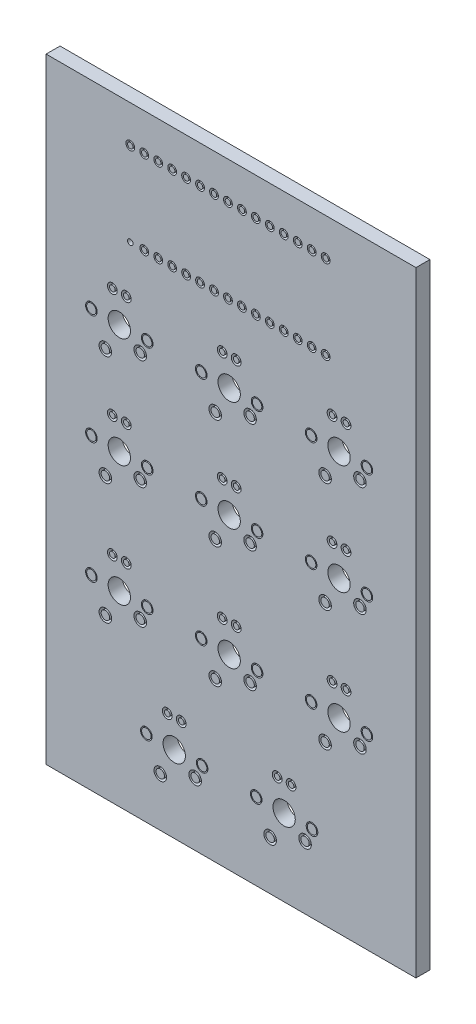
SolidWorks part; units mm, degrees
ref_plane "Front Plane" through (0, 0, 0) normal (0, 0, 1) x (1, 0, 0)
ref_plane "Top Plane" through (0, 0, 0) normal (0, 1, 0) x (1, 0, 0)
ref_plane "Right Plane" through (0, 0, 0) normal (1, 0, 0) x (0, 0, -1)
sketch "Sketch2" plane through (0, 0, 0) normal (0, 0, 1) x (1, 0, 0)
  line L1 (0.6731, 111.9988) -> (68.0009, 111.9988)
  line L2 (68.0009, 111.9988) -> (68.0009, 0)
  line L3 (68.0009, 0) -> (0.6731, 0)
  line L4 (0.6731, 0) -> (0.6731, 40.5511)
  line L5 (0.6731, 40.5511) -> (0.6731, 111.9988)
  line L6 (17.8075, 52.698) -> (17.8125, 52.698)
  line L8 (17.8075, 54.222) -> (17.8125, 54.222)
  line L10 (11.4575, 50.158) -> (11.4625, 50.158)
  line L12 (11.4575, 51.682) -> (11.4625, 51.682)
  line L14 (19.0775, 55.1427) -> (19.0825, 55.1427)
  line L16 (19.0775, 56.8572) -> (19.0825, 56.8572)
  line L18 (8.9175, 55.1427) -> (8.9225, 55.1427)
  line L20 (8.9175, 56.8572) -> (8.9225, 56.8572)
  line L22 (15.2675, 60.572) -> (15.2725, 60.572)
  line L24 (15.2675, 61.588) -> (15.2725, 61.588)
  line L26 (12.7275, 60.572) -> (12.7325, 60.572)
  line L28 (12.7275, 61.588) -> (12.7325, 61.588)
  line L30 (37.8074, 52.698) -> (37.8125, 52.698)
  line L32 (37.8074, 54.222) -> (37.8125, 54.222)
  line L34 (31.4574, 50.158) -> (31.4625, 50.158)
  line L36 (31.4574, 51.682) -> (31.4625, 51.682)
  line L38 (39.0774, 55.1427) -> (39.0825, 55.1427)
  line L40 (39.0774, 56.8572) -> (39.0825, 56.8572)
  line L42 (28.9174, 55.1427) -> (28.9225, 55.1427)
  line L44 (28.9174, 56.8572) -> (28.9225, 56.8572)
  line L46 (35.2674, 60.572) -> (35.2725, 60.572)
  line L48 (35.2674, 61.588) -> (35.2725, 61.588)
  line L50 (32.7274, 60.572) -> (32.7325, 60.572)
  line L52 (32.7274, 61.588) -> (32.7325, 61.588)
  line L54 (17.8075, 30.698) -> (17.8125, 30.698)
  line L56 (17.8075, 32.222) -> (17.8125, 32.222)
  line L58 (11.4575, 28.158) -> (11.4625, 28.158)
  line L60 (11.4575, 29.682) -> (11.4625, 29.682)
  line L62 (19.0775, 33.1427) -> (19.0825, 33.1427)
  line L64 (19.0775, 34.8572) -> (19.0825, 34.8572)
  line L66 (8.9175, 33.1427) -> (8.9225, 33.1427)
  line L68 (8.9175, 34.8572) -> (8.9225, 34.8572)
  line L70 (15.2675, 38.572) -> (15.2725, 38.572)
  line L72 (15.2675, 39.588) -> (15.2725, 39.588)
  line L74 (12.7275, 38.572) -> (12.7325, 38.572)
  line L76 (12.7275, 39.588) -> (12.7325, 39.588)
  line L78 (37.8074, 30.698) -> (37.8125, 30.698)
  line L80 (37.8074, 32.222) -> (37.8125, 32.222)
  line L82 (31.4574, 28.158) -> (31.4625, 28.158)
  line L84 (31.4574, 29.682) -> (31.4625, 29.682)
  line L86 (39.0774, 33.1427) -> (39.0825, 33.1427)
  line L88 (39.0774, 34.8572) -> (39.0825, 34.8572)
  line L90 (28.9174, 33.1427) -> (28.9225, 33.1427)
  line L92 (28.9174, 34.8572) -> (28.9225, 34.8572)
  line L94 (35.2674, 38.572) -> (35.2725, 38.572)
  line L96 (35.2674, 39.588) -> (35.2725, 39.588)
  line L98 (32.7274, 38.572) -> (32.7325, 38.572)
  line L100 (32.7274, 39.588) -> (32.7325, 39.588)
  line L102 (57.8075, 52.698) -> (57.8125, 52.698)
  line L104 (57.8075, 54.222) -> (57.8125, 54.222)
  line L106 (51.4575, 50.158) -> (51.4625, 50.158)
  line L108 (51.4575, 51.682) -> (51.4625, 51.682)
  line L110 (59.0775, 55.1427) -> (59.0825, 55.1427)
  line L112 (59.0775, 56.8572) -> (59.0825, 56.8572)
  line L114 (48.9175, 55.1427) -> (48.9225, 55.1427)
  line L116 (48.9175, 56.8572) -> (48.9225, 56.8572)
  line L118 (55.2675, 60.572) -> (55.2725, 60.572)
  line L120 (55.2675, 61.588) -> (55.2725, 61.588)
  line L122 (52.7275, 60.572) -> (52.7325, 60.572)
  line L124 (52.7275, 61.588) -> (52.7325, 61.588)
  line L126 (57.8075, 30.698) -> (57.8125, 30.698)
  line L128 (57.8075, 32.222) -> (57.8125, 32.222)
  line L130 (51.4575, 28.158) -> (51.4625, 28.158)
  line L132 (51.4575, 29.682) -> (51.4625, 29.682)
  line L134 (59.0775, 33.1427) -> (59.0825, 33.1427)
  line L136 (59.0775, 34.8572) -> (59.0825, 34.8572)
  line L138 (48.9175, 33.1427) -> (48.9225, 33.1427)
  line L140 (48.9175, 34.8572) -> (48.9225, 34.8572)
  line L142 (55.2675, 38.572) -> (55.2725, 38.572)
  line L144 (55.2675, 39.588) -> (55.2725, 39.588)
  line L146 (52.7275, 38.572) -> (52.7325, 38.572)
  line L148 (52.7275, 39.588) -> (52.7325, 39.588)
  line L150 (27.8074, 10.698) -> (27.8125, 10.698)
  line L152 (27.8074, 12.222) -> (27.8125, 12.222)
  line L154 (21.4574, 8.158) -> (21.4625, 8.158)
  line L156 (21.4574, 9.682) -> (21.4625, 9.682)
  line L158 (29.0774, 13.1427) -> (29.0825, 13.1427)
  line L160 (29.0774, 14.8572) -> (29.0825, 14.8572)
  line L162 (18.9174, 13.1427) -> (18.9225, 13.1427)
  line L164 (18.9174, 14.8572) -> (18.9225, 14.8572)
  line L166 (25.2674, 18.572) -> (25.2725, 18.572)
  line L168 (25.2674, 19.588) -> (25.2725, 19.588)
  line L170 (22.7274, 18.572) -> (22.7325, 18.572)
  line L172 (22.7274, 19.588) -> (22.7325, 19.588)
  line L174 (47.8074, 10.698) -> (47.8125, 10.698)
  line L176 (47.8074, 12.222) -> (47.8125, 12.222)
  line L178 (41.4574, 8.158) -> (41.4625, 8.158)
  line L180 (41.4574, 9.682) -> (41.4625, 9.682)
  line L182 (49.0774, 13.1427) -> (49.0825, 13.1427)
  line L184 (49.0774, 14.8572) -> (49.0825, 14.8572)
  line L186 (38.9174, 13.1427) -> (38.9225, 13.1427)
  line L188 (38.9174, 14.8572) -> (38.9225, 14.8572)
  line L190 (45.2674, 18.572) -> (45.2725, 18.572)
  line L192 (45.2674, 19.588) -> (45.2725, 19.588)
  line L194 (42.7274, 18.572) -> (42.7325, 18.572)
  line L196 (42.7274, 19.588) -> (42.7325, 19.588)
  line L198 (17.8075, 72.698) -> (17.8125, 72.698)
  line L200 (17.8075, 74.222) -> (17.8125, 74.222)
  line L202 (11.4575, 70.158) -> (11.4625, 70.158)
  line L204 (11.4575, 71.682) -> (11.4625, 71.682)
  line L206 (19.0775, 75.1428) -> (19.0825, 75.1428)
  line L208 (19.0775, 76.8573) -> (19.0825, 76.8573)
  line L210 (8.9175, 75.1428) -> (8.9225, 75.1428)
  line L212 (8.9175, 76.8573) -> (8.9225, 76.8573)
  line L214 (15.2675, 80.572) -> (15.2725, 80.572)
  line L216 (15.2675, 81.588) -> (15.2725, 81.588)
  line L218 (12.7275, 80.572) -> (12.7325, 80.572)
  line L220 (12.7275, 81.588) -> (12.7325, 81.588)
  line L222 (37.8074, 72.698) -> (37.8125, 72.698)
  line L224 (37.8074, 74.222) -> (37.8125, 74.222)
  line L226 (31.4574, 70.158) -> (31.4625, 70.158)
  line L228 (31.4574, 71.682) -> (31.4625, 71.682)
  line L230 (39.0774, 75.1428) -> (39.0825, 75.1428)
  line L232 (39.0774, 76.8573) -> (39.0825, 76.8573)
  line L234 (28.9174, 75.1428) -> (28.9225, 75.1428)
  line L236 (28.9174, 76.8573) -> (28.9225, 76.8573)
  line L238 (35.2674, 80.572) -> (35.2725, 80.572)
  line L240 (35.2674, 81.588) -> (35.2725, 81.588)
  line L242 (32.7274, 80.572) -> (32.7325, 80.572)
  line L244 (32.7274, 81.588) -> (32.7325, 81.588)
  line L246 (57.8075, 72.698) -> (57.8125, 72.698)
  line L248 (57.8075, 74.222) -> (57.8125, 74.222)
  line L250 (51.4575, 70.158) -> (51.4625, 70.158)
  line L252 (51.4575, 71.682) -> (51.4625, 71.682)
  line L254 (59.0775, 75.1428) -> (59.0825, 75.1428)
  line L256 (59.0775, 76.8573) -> (59.0825, 76.8573)
  line L258 (48.9175, 75.1428) -> (48.9225, 75.1428)
  line L260 (48.9175, 76.8573) -> (48.9225, 76.8573)
  line L262 (55.2675, 80.572) -> (55.2725, 80.572)
  line L264 (55.2675, 81.588) -> (55.2725, 81.588)
  line L266 (52.7275, 80.572) -> (52.7325, 80.572)
  line L268 (52.7275, 81.588) -> (52.7325, 81.588)
  circle A0 centre (18.54, 90) radius 0.5
  circle A1 centre (18.54, 90) radius 0.8
  circle A2 centre (21.08, 90) radius 0.5
  circle A3 centre (21.08, 90) radius 0.8
  circle A4 centre (23.62, 90) radius 0.5
  circle A5 centre (23.62, 90) radius 0.8
  circle A6 centre (26.16, 90) radius 0.5
  circle A7 centre (26.16, 90) radius 0.8
  circle A8 centre (28.7, 90) radius 0.5
  circle A9 centre (28.7, 90) radius 0.8
  circle A10 centre (31.24, 90) radius 0.5
  circle A11 centre (31.24, 90) radius 0.8
  circle A12 centre (33.78, 90) radius 0.5
  circle A13 centre (33.78, 90) radius 0.8
  circle A14 centre (36.32, 90) radius 0.5
  circle A15 centre (36.32, 90) radius 0.8
  circle A16 centre (38.86, 90) radius 0.5
  circle A17 centre (38.86, 90) radius 0.8
  circle A18 centre (41.4, 90) radius 0.5
  circle A19 centre (41.4, 90) radius 0.8
  circle A20 centre (43.94, 90) radius 0.5
  circle A21 centre (43.94, 90) radius 0.8
  circle A22 centre (46.48, 90) radius 0.5
  circle A23 centre (46.48, 90) radius 0.8
  circle A24 centre (49.02, 90) radius 0.5
  circle A25 centre (49.02, 90) radius 0.8
  circle A26 centre (51.56, 90) radius 0.5
  circle A27 centre (51.56, 90) radius 0.8
  circle A28 centre (51.56, 105.24) radius 0.5
  circle A29 centre (51.56, 105.24) radius 0.8
  circle A30 centre (49.02, 105.24) radius 0.5
  circle A31 centre (49.02, 105.24) radius 0.8
  circle A32 centre (46.48, 105.24) radius 0.5
  circle A33 centre (46.48, 105.24) radius 0.8
  circle A34 centre (43.94, 105.24) radius 0.5
  circle A35 centre (43.94, 105.24) radius 0.8
  circle A36 centre (41.4, 105.24) radius 0.5
  circle A37 centre (41.4, 105.24) radius 0.8
  circle A38 centre (38.86, 105.24) radius 0.5
  circle A39 centre (38.86, 105.24) radius 0.8
  circle A40 centre (36.32, 105.24) radius 0.5
  circle A41 centre (36.32, 105.24) radius 0.8
  circle A42 centre (33.78, 105.24) radius 0.5
  circle A43 centre (33.78, 105.24) radius 0.8
  circle A44 centre (31.24, 105.24) radius 0.5
  circle A45 centre (31.24, 105.24) radius 0.8
  circle A46 centre (28.7, 105.24) radius 0.5
  circle A47 centre (28.7, 105.24) radius 0.8
  circle A48 centre (26.16, 105.24) radius 0.5
  circle A49 centre (26.16, 105.24) radius 0.8
  circle A50 centre (23.62, 105.24) radius 0.5
  circle A51 centre (23.62, 105.24) radius 0.8
  circle A52 centre (21.08, 105.24) radius 0.5
  circle A53 centre (21.08, 105.24) radius 0.8
  circle A54 centre (18.54, 105.24) radius 0.5
  circle A55 centre (18.54, 105.24) radius 0.8
  circle A56 centre (16, 105.24) radius 0.5
  circle A57 centre (16, 105.24) radius 0.8
  arc A58 (17.8125, 52.698) -> (17.8125, 54.222) centre (17.8125, 53.46) ccw
  arc A59 (17.8075, 54.222) -> (17.8075, 52.698) centre (17.8075, 53.46) ccw
  circle A60 centre (17.81, 53.46) radius 1.143
  arc A61 (11.4625, 50.158) -> (11.4625, 51.682) centre (11.4625, 50.92) ccw
  arc A62 (11.4575, 51.682) -> (11.4575, 50.158) centre (11.4575, 50.92) ccw
  circle A63 centre (11.46, 50.92) radius 1.143
  arc A64 (19.0825, 55.1427) -> (19.0825, 56.8572) centre (19.0825, 56) ccw
  arc A65 (19.0775, 56.8572) -> (19.0775, 55.1427) centre (19.0775, 56) ccw
  circle A66 centre (19.08, 56) radius 1.0571
  arc A67 (8.9225, 55.1427) -> (8.9225, 56.8572) centre (8.9225, 56) ccw
  arc A68 (8.9175, 56.8572) -> (8.9175, 55.1427) centre (8.9175, 56) ccw
  circle A69 centre (8.92, 56) radius 1.0571
  arc A70 (15.2725, 60.572) -> (15.2725, 61.588) centre (15.2725, 61.08) ccw
  arc A71 (15.2675, 61.588) -> (15.2675, 60.572) centre (15.2675, 61.08) ccw
  circle A72 centre (15.27, 61.08) radius 0.889
  arc A73 (12.7325, 60.572) -> (12.7325, 61.588) centre (12.7325, 61.08) ccw
  arc A74 (12.7275, 61.588) -> (12.7275, 60.572) centre (12.7275, 61.08) ccw
  circle A75 centre (12.73, 61.08) radius 0.889
  arc A76 (37.8125, 52.698) -> (37.8125, 54.222) centre (37.8125, 53.46) ccw
  arc A77 (37.8074, 54.222) -> (37.8074, 52.698) centre (37.8074, 53.46) ccw
  circle A78 centre (37.81, 53.46) radius 1.143
  arc A79 (31.4625, 50.158) -> (31.4625, 51.682) centre (31.4625, 50.92) ccw
  arc A80 (31.4574, 51.682) -> (31.4574, 50.158) centre (31.4574, 50.92) ccw
  circle A81 centre (31.46, 50.92) radius 1.143
  arc A82 (39.0825, 55.1427) -> (39.0825, 56.8572) centre (39.0825, 56) ccw
  arc A83 (39.0774, 56.8572) -> (39.0774, 55.1427) centre (39.0774, 56) ccw
  circle A84 centre (39.08, 56) radius 1.0571
  arc A85 (28.9225, 55.1427) -> (28.9225, 56.8572) centre (28.9225, 56) ccw
  arc A86 (28.9174, 56.8572) -> (28.9174, 55.1427) centre (28.9174, 56) ccw
  circle A87 centre (28.92, 56) radius 1.0571
  arc A88 (35.2725, 60.572) -> (35.2725, 61.588) centre (35.2725, 61.08) ccw
  arc A89 (35.2674, 61.588) -> (35.2674, 60.572) centre (35.2674, 61.08) ccw
  circle A90 centre (35.27, 61.08) radius 0.889
  arc A91 (32.7325, 60.572) -> (32.7325, 61.588) centre (32.7325, 61.08) ccw
  arc A92 (32.7274, 61.588) -> (32.7274, 60.572) centre (32.7274, 61.08) ccw
  circle A93 centre (32.73, 61.08) radius 0.889
  arc A94 (17.8125, 30.698) -> (17.8125, 32.222) centre (17.8125, 31.46) ccw
  arc A95 (17.8075, 32.222) -> (17.8075, 30.698) centre (17.8075, 31.46) ccw
  circle A96 centre (17.81, 31.46) radius 1.143
  arc A97 (11.4625, 28.158) -> (11.4625, 29.682) centre (11.4625, 28.92) ccw
  arc A98 (11.4575, 29.682) -> (11.4575, 28.158) centre (11.4575, 28.92) ccw
  circle A99 centre (11.46, 28.92) radius 1.143
  arc A100 (19.0825, 33.1427) -> (19.0825, 34.8572) centre (19.0825, 34) ccw
  arc A101 (19.0775, 34.8572) -> (19.0775, 33.1427) centre (19.0775, 34) ccw
  circle A102 centre (19.08, 34) radius 1.0571
  arc A103 (8.9225, 33.1427) -> (8.9225, 34.8572) centre (8.9225, 34) ccw
  arc A104 (8.9175, 34.8572) -> (8.9175, 33.1427) centre (8.9175, 34) ccw
  circle A105 centre (8.92, 34) radius 1.0571
  arc A106 (15.2725, 38.572) -> (15.2725, 39.588) centre (15.2725, 39.08) ccw
  arc A107 (15.2675, 39.588) -> (15.2675, 38.572) centre (15.2675, 39.08) ccw
  circle A108 centre (15.27, 39.08) radius 0.889
  arc A109 (12.7325, 38.572) -> (12.7325, 39.588) centre (12.7325, 39.08) ccw
  arc A110 (12.7275, 39.588) -> (12.7275, 38.572) centre (12.7275, 39.08) ccw
  circle A111 centre (12.73, 39.08) radius 0.889
  arc A112 (37.8125, 30.698) -> (37.8125, 32.222) centre (37.8125, 31.46) ccw
  arc A113 (37.8074, 32.222) -> (37.8074, 30.698) centre (37.8074, 31.46) ccw
  circle A114 centre (37.81, 31.46) radius 1.143
  arc A115 (31.4625, 28.158) -> (31.4625, 29.682) centre (31.4625, 28.92) ccw
  arc A116 (31.4574, 29.682) -> (31.4574, 28.158) centre (31.4574, 28.92) ccw
  circle A117 centre (31.46, 28.92) radius 1.143
  arc A118 (39.0825, 33.1427) -> (39.0825, 34.8572) centre (39.0825, 34) ccw
  arc A119 (39.0774, 34.8572) -> (39.0774, 33.1427) centre (39.0774, 34) ccw
  circle A120 centre (39.08, 34) radius 1.0571
  arc A121 (28.9225, 33.1427) -> (28.9225, 34.8572) centre (28.9225, 34) ccw
  arc A122 (28.9174, 34.8572) -> (28.9174, 33.1427) centre (28.9174, 34) ccw
  circle A123 centre (28.92, 34) radius 1.0571
  arc A124 (35.2725, 38.572) -> (35.2725, 39.588) centre (35.2725, 39.08) ccw
  arc A125 (35.2674, 39.588) -> (35.2674, 38.572) centre (35.2674, 39.08) ccw
  circle A126 centre (35.27, 39.08) radius 0.889
  arc A127 (32.7325, 38.572) -> (32.7325, 39.588) centre (32.7325, 39.08) ccw
  arc A128 (32.7274, 39.588) -> (32.7274, 38.572) centre (32.7274, 39.08) ccw
  circle A129 centre (32.73, 39.08) radius 0.889
  arc A130 (57.8125, 52.698) -> (57.8125, 54.222) centre (57.8125, 53.46) ccw
  arc A131 (57.8075, 54.222) -> (57.8075, 52.698) centre (57.8075, 53.46) ccw
  circle A132 centre (57.81, 53.46) radius 1.143
  arc A133 (51.4625, 50.158) -> (51.4625, 51.682) centre (51.4625, 50.92) ccw
  arc A134 (51.4575, 51.682) -> (51.4575, 50.158) centre (51.4575, 50.92) ccw
  circle A135 centre (51.46, 50.92) radius 1.143
  arc A136 (59.0825, 55.1427) -> (59.0825, 56.8572) centre (59.0825, 56) ccw
  arc A137 (59.0775, 56.8572) -> (59.0775, 55.1427) centre (59.0775, 56) ccw
  circle A138 centre (59.08, 56) radius 1.0571
  arc A139 (48.9225, 55.1427) -> (48.9225, 56.8572) centre (48.9225, 56) ccw
  arc A140 (48.9175, 56.8572) -> (48.9175, 55.1427) centre (48.9175, 56) ccw
  circle A141 centre (48.92, 56) radius 1.0571
  arc A142 (55.2725, 60.572) -> (55.2725, 61.588) centre (55.2725, 61.08) ccw
  arc A143 (55.2675, 61.588) -> (55.2675, 60.572) centre (55.2675, 61.08) ccw
  circle A144 centre (55.27, 61.08) radius 0.889
  arc A145 (52.7325, 60.572) -> (52.7325, 61.588) centre (52.7325, 61.08) ccw
  arc A146 (52.7275, 61.588) -> (52.7275, 60.572) centre (52.7275, 61.08) ccw
  circle A147 centre (52.73, 61.08) radius 0.889
  arc A148 (57.8125, 30.698) -> (57.8125, 32.222) centre (57.8125, 31.46) ccw
  arc A149 (57.8075, 32.222) -> (57.8075, 30.698) centre (57.8075, 31.46) ccw
  circle A150 centre (57.81, 31.46) radius 1.143
  arc A151 (51.4625, 28.158) -> (51.4625, 29.682) centre (51.4625, 28.92) ccw
  arc A152 (51.4575, 29.682) -> (51.4575, 28.158) centre (51.4575, 28.92) ccw
  circle A153 centre (51.46, 28.92) radius 1.143
  arc A154 (59.0825, 33.1427) -> (59.0825, 34.8572) centre (59.0825, 34) ccw
  arc A155 (59.0775, 34.8572) -> (59.0775, 33.1427) centre (59.0775, 34) ccw
  circle A156 centre (59.08, 34) radius 1.0571
  arc A157 (48.9225, 33.1427) -> (48.9225, 34.8572) centre (48.9225, 34) ccw
  arc A158 (48.9175, 34.8572) -> (48.9175, 33.1427) centre (48.9175, 34) ccw
  circle A159 centre (48.92, 34) radius 1.0571
  arc A160 (55.2725, 38.572) -> (55.2725, 39.588) centre (55.2725, 39.08) ccw
  arc A161 (55.2675, 39.588) -> (55.2675, 38.572) centre (55.2675, 39.08) ccw
  circle A162 centre (55.27, 39.08) radius 0.889
  arc A163 (52.7325, 38.572) -> (52.7325, 39.588) centre (52.7325, 39.08) ccw
  arc A164 (52.7275, 39.588) -> (52.7275, 38.572) centre (52.7275, 39.08) ccw
  circle A165 centre (52.73, 39.08) radius 0.889
  arc A166 (27.8125, 10.698) -> (27.8125, 12.222) centre (27.8125, 11.46) ccw
  arc A167 (27.8074, 12.222) -> (27.8074, 10.698) centre (27.8074, 11.46) ccw
  circle A168 centre (27.81, 11.46) radius 1.143
  arc A169 (21.4625, 8.158) -> (21.4625, 9.682) centre (21.4625, 8.92) ccw
  arc A170 (21.4574, 9.682) -> (21.4574, 8.158) centre (21.4574, 8.92) ccw
  circle A171 centre (21.46, 8.92) radius 1.143
  arc A172 (29.0825, 13.1427) -> (29.0825, 14.8572) centre (29.0825, 14) ccw
  arc A173 (29.0774, 14.8572) -> (29.0774, 13.1427) centre (29.0774, 14) ccw
  circle A174 centre (29.08, 14) radius 1.0571
  arc A175 (18.9225, 13.1427) -> (18.9225, 14.8572) centre (18.9225, 14) ccw
  arc A176 (18.9174, 14.8572) -> (18.9174, 13.1427) centre (18.9174, 14) ccw
  circle A177 centre (18.92, 14) radius 1.0571
  arc A178 (25.2725, 18.572) -> (25.2725, 19.588) centre (25.2725, 19.08) ccw
  arc A179 (25.2674, 19.588) -> (25.2674, 18.572) centre (25.2674, 19.08) ccw
  circle A180 centre (25.27, 19.08) radius 0.889
  arc A181 (22.7325, 18.572) -> (22.7325, 19.588) centre (22.7325, 19.08) ccw
  arc A182 (22.7274, 19.588) -> (22.7274, 18.572) centre (22.7274, 19.08) ccw
  circle A183 centre (22.73, 19.08) radius 0.889
  arc A184 (47.8125, 10.698) -> (47.8125, 12.222) centre (47.8125, 11.46) ccw
  arc A185 (47.8074, 12.222) -> (47.8074, 10.698) centre (47.8074, 11.46) ccw
  circle A186 centre (47.81, 11.46) radius 1.143
  arc A187 (41.4625, 8.158) -> (41.4625, 9.682) centre (41.4625, 8.92) ccw
  arc A188 (41.4574, 9.682) -> (41.4574, 8.158) centre (41.4574, 8.92) ccw
  circle A189 centre (41.46, 8.92) radius 1.143
  arc A190 (49.0825, 13.1427) -> (49.0825, 14.8572) centre (49.0825, 14) ccw
  arc A191 (49.0774, 14.8572) -> (49.0774, 13.1427) centre (49.0774, 14) ccw
  circle A192 centre (49.08, 14) radius 1.0571
  arc A193 (38.9225, 13.1427) -> (38.9225, 14.8572) centre (38.9225, 14) ccw
  arc A194 (38.9174, 14.8572) -> (38.9174, 13.1427) centre (38.9174, 14) ccw
  circle A195 centre (38.92, 14) radius 1.0571
  arc A196 (45.2725, 18.572) -> (45.2725, 19.588) centre (45.2725, 19.08) ccw
  arc A197 (45.2674, 19.588) -> (45.2674, 18.572) centre (45.2674, 19.08) ccw
  circle A198 centre (45.27, 19.08) radius 0.889
  arc A199 (42.7325, 18.572) -> (42.7325, 19.588) centre (42.7325, 19.08) ccw
  arc A200 (42.7274, 19.588) -> (42.7274, 18.572) centre (42.7274, 19.08) ccw
  circle A201 centre (42.73, 19.08) radius 0.889
  arc A202 (17.8125, 72.698) -> (17.8125, 74.222) centre (17.8125, 73.46) ccw
  arc A203 (17.8075, 74.222) -> (17.8075, 72.698) centre (17.8075, 73.46) ccw
  circle A204 centre (17.81, 73.46) radius 1.143
  arc A205 (11.4625, 70.158) -> (11.4625, 71.682) centre (11.4625, 70.92) ccw
  arc A206 (11.4575, 71.682) -> (11.4575, 70.158) centre (11.4575, 70.92) ccw
  circle A207 centre (11.46, 70.92) radius 1.143
  arc A208 (19.0825, 75.1428) -> (19.0825, 76.8573) centre (19.0825, 76) ccw
  arc A209 (19.0775, 76.8573) -> (19.0775, 75.1428) centre (19.0775, 76) ccw
  circle A210 centre (19.08, 76) radius 1.0571
  arc A211 (8.9225, 75.1428) -> (8.9225, 76.8573) centre (8.9225, 76) ccw
  arc A212 (8.9175, 76.8573) -> (8.9175, 75.1428) centre (8.9175, 76) ccw
  circle A213 centre (8.92, 76) radius 1.0571
  arc A214 (15.2725, 80.572) -> (15.2725, 81.588) centre (15.2725, 81.08) ccw
  arc A215 (15.2675, 81.588) -> (15.2675, 80.572) centre (15.2675, 81.08) ccw
  circle A216 centre (15.27, 81.08) radius 0.889
  arc A217 (12.7325, 80.572) -> (12.7325, 81.588) centre (12.7325, 81.08) ccw
  arc A218 (12.7275, 81.588) -> (12.7275, 80.572) centre (12.7275, 81.08) ccw
  circle A219 centre (12.73, 81.08) radius 0.889
  arc A220 (37.8125, 72.698) -> (37.8125, 74.222) centre (37.8125, 73.46) ccw
  arc A221 (37.8074, 74.222) -> (37.8074, 72.698) centre (37.8074, 73.46) ccw
  circle A222 centre (37.81, 73.46) radius 1.143
  arc A223 (31.4625, 70.158) -> (31.4625, 71.682) centre (31.4625, 70.92) ccw
  arc A224 (31.4574, 71.682) -> (31.4574, 70.158) centre (31.4574, 70.92) ccw
  circle A225 centre (31.46, 70.92) radius 1.143
  arc A226 (39.0825, 75.1428) -> (39.0825, 76.8573) centre (39.0825, 76) ccw
  arc A227 (39.0774, 76.8573) -> (39.0774, 75.1428) centre (39.0774, 76) ccw
  circle A228 centre (39.08, 76) radius 1.0571
  arc A229 (28.9225, 75.1428) -> (28.9225, 76.8573) centre (28.9225, 76) ccw
  arc A230 (28.9174, 76.8573) -> (28.9174, 75.1428) centre (28.9174, 76) ccw
  circle A231 centre (28.92, 76) radius 1.0571
  arc A232 (35.2725, 80.572) -> (35.2725, 81.588) centre (35.2725, 81.08) ccw
  arc A233 (35.2674, 81.588) -> (35.2674, 80.572) centre (35.2674, 81.08) ccw
  circle A234 centre (35.27, 81.08) radius 0.889
  arc A235 (32.7325, 80.572) -> (32.7325, 81.588) centre (32.7325, 81.08) ccw
  arc A236 (32.7274, 81.588) -> (32.7274, 80.572) centre (32.7274, 81.08) ccw
  circle A237 centre (32.73, 81.08) radius 0.889
  arc A238 (57.8125, 72.698) -> (57.8125, 74.222) centre (57.8125, 73.46) ccw
  arc A239 (57.8075, 74.222) -> (57.8075, 72.698) centre (57.8075, 73.46) ccw
  circle A240 centre (57.81, 73.46) radius 1.143
  arc A241 (51.4625, 70.158) -> (51.4625, 71.682) centre (51.4625, 70.92) ccw
  arc A242 (51.4575, 71.682) -> (51.4575, 70.158) centre (51.4575, 70.92) ccw
  circle A243 centre (51.46, 70.92) radius 1.143
  arc A244 (59.0825, 75.1428) -> (59.0825, 76.8573) centre (59.0825, 76) ccw
  arc A245 (59.0775, 76.8573) -> (59.0775, 75.1428) centre (59.0775, 76) ccw
  circle A246 centre (59.08, 76) radius 1.0571
  arc A247 (48.9225, 75.1428) -> (48.9225, 76.8573) centre (48.9225, 76) ccw
  arc A248 (48.9175, 76.8573) -> (48.9175, 75.1428) centre (48.9175, 76) ccw
  circle A249 centre (48.92, 76) radius 1.0571
  arc A250 (55.2725, 80.572) -> (55.2725, 81.588) centre (55.2725, 81.08) ccw
  arc A251 (55.2675, 81.588) -> (55.2675, 80.572) centre (55.2675, 81.08) ccw
  circle A252 centre (55.27, 81.08) radius 0.889
  arc A253 (52.7325, 80.572) -> (52.7325, 81.588) centre (52.7325, 81.08) ccw
  arc A254 (52.7275, 81.588) -> (52.7275, 80.572) centre (52.7275, 81.08) ccw
  circle A255 centre (52.73, 81.08) radius 0.889
  circle A256 centre (16, 90) radius 0.5
  circle A257 centre (14, 56) radius 2.032
  circle A258 centre (34, 56) radius 2.032
  circle A259 centre (14, 34) radius 2.032
  circle A260 centre (34, 34) radius 2.032
  circle A261 centre (54, 56) radius 2.032
  circle A262 centre (54, 34) radius 2.032
  circle A263 centre (24, 14) radius 2.032
  circle A264 centre (44, 14) radius 2.032
  circle A265 centre (14, 76) radius 2.032
  circle A266 centre (34, 76) radius 2.032
  circle A267 centre (54, 76) radius 2.032
  point P0 (0, 0.001)
  point P1 (0.001, 0.001)
  point P2 (0.001, 0)
  point P3 (0, 111.9988)
extrude "Boss-Extrude2" add sketch "Sketch2" along normal blind 2.54
